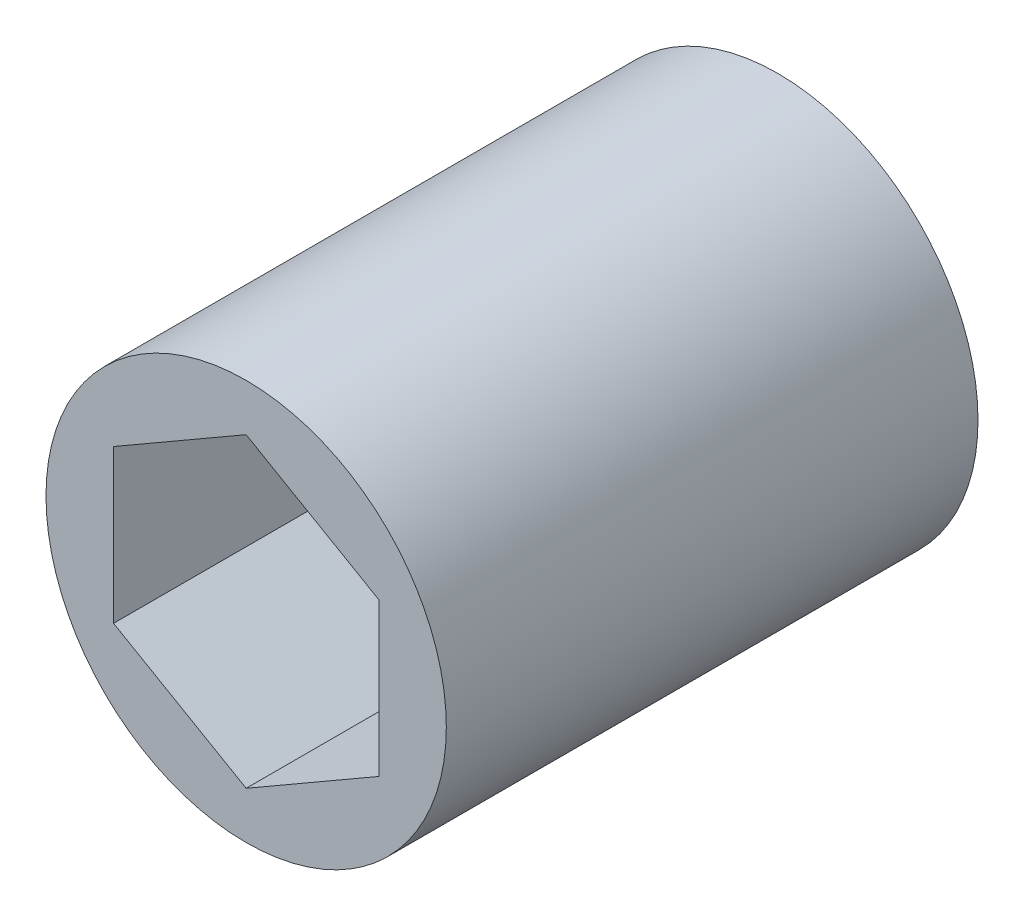
SolidWorks part; units mm, degrees
material "PET"
ref_plane "Front Plane" through (0, 0, 0) normal (0, 0, 1) x (1, 0, 0)
ref_plane "Top Plane" through (0, 0, 0) normal (0, 1, 0) x (1, 0, 0)
ref_plane "Right Plane" through (0, 0, 0) normal (1, 0, 0) x (0, 0, -1)
sketch "Sketch1" plane through (0, 0, 0) normal (0, 0, 1) x (1, 0, 0)
  line L1 (6.731, 3.8861) -> (0, 7.7723)
  line L2 (0, 7.7723) -> (-6.731, 3.8861)
  line L3 (-6.731, 3.8861) -> (-6.731, -3.8861)
  line L4 (-6.731, -3.8861) -> (0, -7.7723)
  line L5 (0, -7.7723) -> (6.731, -3.8861)
  line L6 (6.731, -3.8861) -> (6.731, 3.8861)
  circle A0 centre (0, 0) radius 6.731 construction
  circle A1 centre (0, 0) radius 10.16
  dimension "D1" = 13.462
  dimension "D2" = 20.32
extrude "Boss-Extrude1" add sketch "Sketch1" along normal blind 26.9875
ref_axis "Axis1" through (0, 0, 26.9875) along (0, 0, -1)
